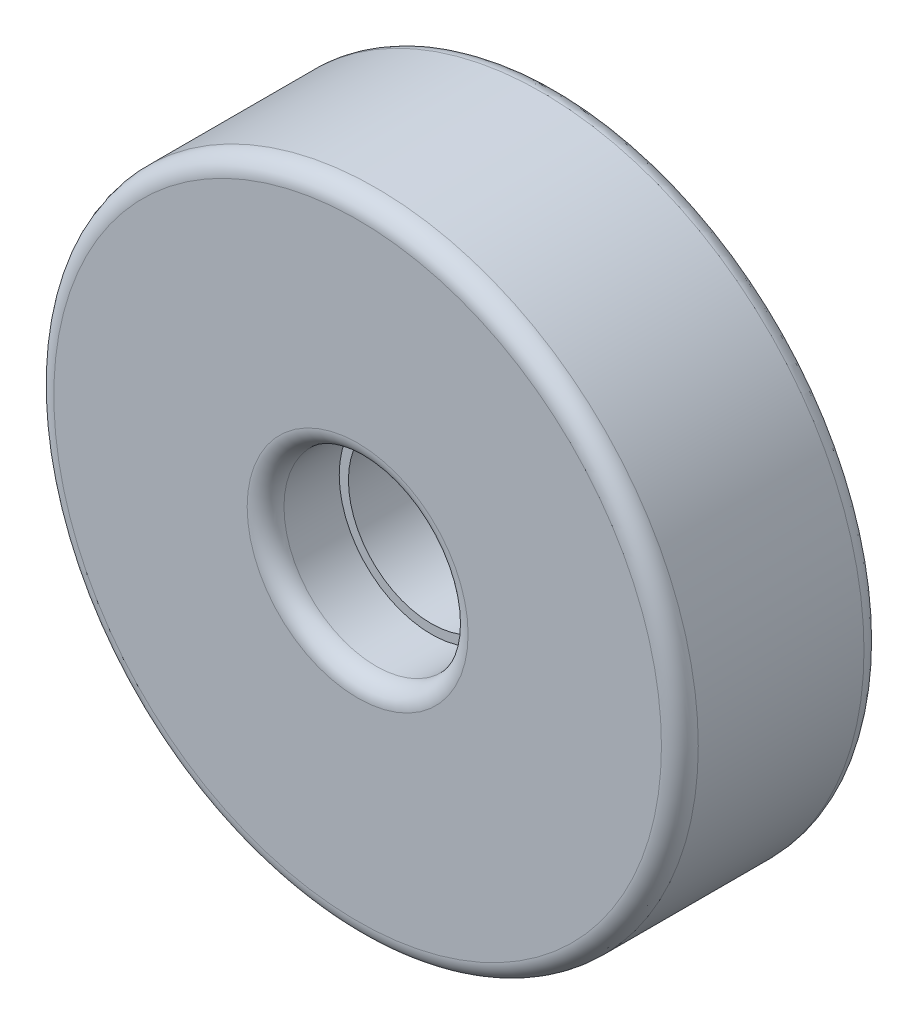
SolidWorks part; units mm, degrees
ref_plane "正面" through (0, 0, 0) normal (0, 0, 1) x (1, 0, 0)
ref_plane "平面" through (0, 0, 0) normal (0, 1, 0) x (1, 0, 0)
ref_plane "右側面" through (0, 0, 0) normal (1, 0, 0) x (0, 0, -1)
sketch "ｽｹｯﾁ1" plane through (0, 0, 0) normal (0, 0, 1) x (1, 0, 0)
  circle A0 centre (0, 0) radius 17.5
  circle A1 centre (0, 0) radius 4.5
  dimension "D1" = 35
  dimension "D2" = 9
extrude "ﾎﾞｽ - 押し出し1" add sketch "ｽｹｯﾁ1" along normal blind 11
sketch "ｽｹｯﾁ2" plane through (0, 0, 11) normal (0, 0, 1) x (1, 0, 0)
  circle A0 centre (0, 0) radius 5
  dimension "D1" = 10
extrude "ｶｯﾄ - 押し出し1" cut sketch "ｽｹｯﾁ2" against normal blind 4 and the other way through all
sketch "ｽｹｯﾁ3" plane through (0, 0, 0) normal (0, 0, -1) x (-1, 0, 0)
  line L0 (-17.5, 0) -> (17.5, 0)
  line L1 (4.4721, -0.5) -> (17.4929, -0.5)
  line L2 (4.4721, 0.5) -> (17.4929, 0.5)
  line L3 (0, 0) -> (8.625, 14.9389)
  line L4 (-2.6691, 3.623) -> (-9.1794, 14.8993)
  line L5 (8.75, -15.1554) -> (-8.75, 15.1554)
  line L6 (-1.8031, 4.123) -> (-8.3134, 15.3993)
  circle A0 centre (0, 0) radius 4.5 construction
  circle A1 centre (0, 0) radius 17.5
  circle A2 centre (0, 0) radius 17.5
  circle A3 centre (0, 0) radius 4.5
  circle A4 centre (0, 0) radius 17.5 construction
  circle A5 centre (0, 0) radius 5.5
  circle A6 centre (0, 0) radius 17.25
  dimension "D4" = 11
  dimension "D5" = 34.5
  dimension "D2" = 0.5
  dimension "D3" = 0.5
  dimension "D6" = 60
  dimension "D1" = 0
sketch "ｽｹｯﾁ4" plane through (0, 0, 0) normal (1, 0, 0) x (0, 0, -1)
  line L0 (0, 0) -> (-11, 0)
  line L1 (-11, 17.5) -> (-11, -17.5) construction
ref_axis "軸1" through (0, 0, 0) along (0, 0, 1)
extrude "ｶｯﾄ - 押し出し3" cut sketch "ｽｹｯﾁ3" against normal blind 10 contours L3 A6 L6 A5 | L2 A6 L3 A5 region at (-0.2397, 11.9096, 0) region at (-10.1941, 6.1624, 0)
pattern_circular "円形ﾊﾟﾀｰﾝ3" count 3 over 360 about axis through (0, 0, 0) along (0, 0, 1) of "ｶｯﾄ - 押し出し3"
fillet "ﾌｨﾚｯﾄ1" radius 1 3 edges at (17.5, 0, 0) (5, 0, 11) (17.5, 0, 11)
sketch "ｽｹｯﾁ6" plane through (0, 0, 0) normal (0, 0, -1) x (-1, 0, 0)
  arc A0 (17.2428, 0.5) -> (-8.1884, 15.1827) centre (0, 0) ccw construction
  arc A1 (5.4772, 0.5) -> (-2.3056, 4.9934) centre (0, 0) ccw construction
  arc A2 (17.2428, 0.5) -> (-8.1884, 15.1827) centre (0, 0) ccw
  arc A3 (5.4772, 0.5) -> (-2.3056, 4.9934) centre (0, 0) ccw
  circle A4 centre (0, 0) radius 4.5
  circle A5 centre (0, 0) radius 5.5
  circle A6 centre (0, 0) radius 17.25
  line M2 (-3.1716, -4.4934) -> (-8.6792, -14.0329)
  arc M3 (-8.6792, -14.0329) -> (-7.8132, -14.5329) centre (0, 0) ccw
  line M4 (-7.8132, -14.5329) -> (-2.3056, -4.9934)
  arc M5 (-2.3056, -4.9934) -> (5.4772, -0.5) centre (0, 0) ccw
  line M6 (5.4772, -0.5) -> (16.4924, -0.5)
  arc M7 (16.4924, -0.5) -> (16.4924, 0.5) centre (0, 0) ccw
  line M8 (16.4924, 0.5) -> (5.4772, 0.5)
  arc M9 (5.4772, 0.5) -> (-2.3056, 4.9934) centre (0, 0) ccw
  line M10 (-2.3056, 4.9934) -> (-7.8132, 14.5329)
  arc M11 (-7.8132, 14.5329) -> (-8.6792, 14.0329) centre (0, 0) ccw
  line M12 (-8.6792, 14.0329) -> (-3.1716, 4.4934)
  arc M13 (-3.1716, 4.4934) -> (-3.1716, -4.4934) centre (0, 0) ccw
  dimension "D1" = 9
extrude "ｶｯﾄ - 押し出し4" cut sketch "ｽｹｯﾁ6" against normal blind 1 contours A5 M10 M11 M12 | A2 A6 M2 M13 M12 M11 M10 M9 M8 M7 M6 M5 M4 M3 | A5 M2 M3 M4 | A5 M6 M7 M8 region at (-16.7603, 0.243, 0) region at (-10.9949, 0, 0) region at (5.4975, 9.5219, 0) region at (5.4975, -9.5219, 0)
sketch "ｽｹｯﾁ7" plane through (0, 0, 0) normal (0, 0, -1) x (-1, 0, 0)
  circle A0 centre (0, 0) radius 4.5
  circle A1 centre (0, 0) radius 5.5
  dimension "D1" = 9
  dimension "D2" = 11
extrude "ﾎﾞｽ - 押し出し2" add sketch "ｽｹｯﾁ7" along normal blind 1
